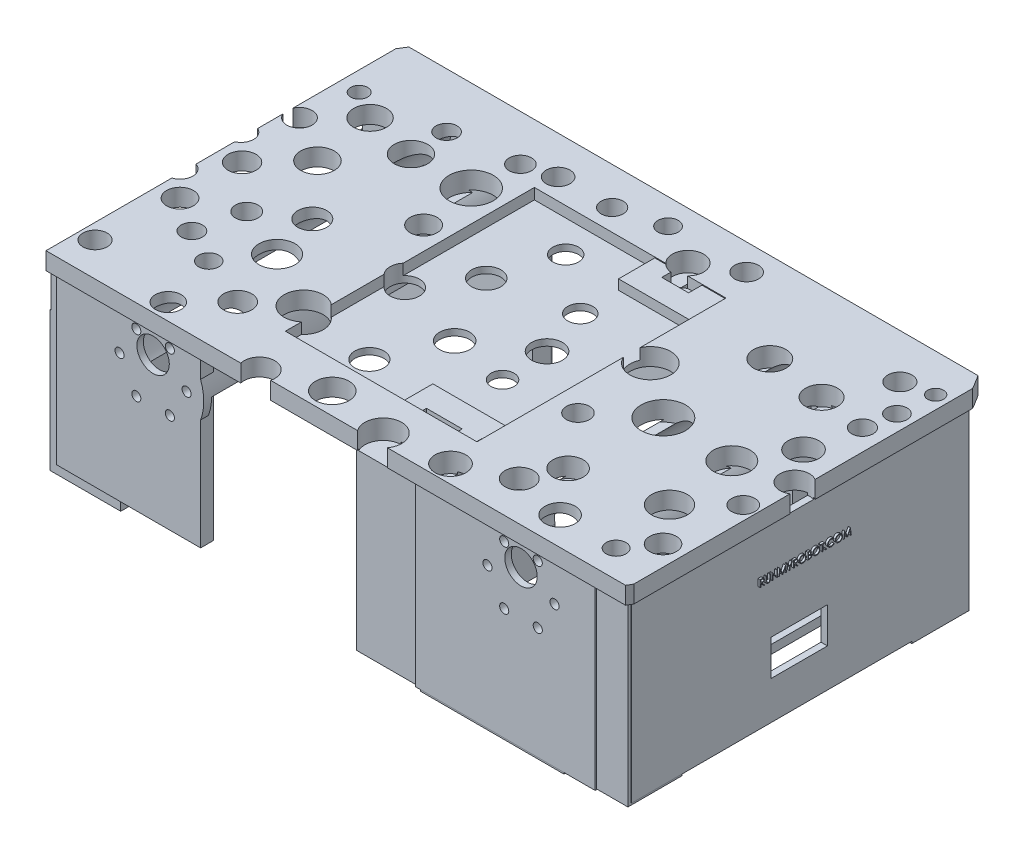
SolidWorks part; units mm, degrees
ref_plane "Front Plane" through (0, 0, 0) normal (0, 0, 1) x (1, 0, 0)
ref_plane "Top Plane" through (0, 0, 0) normal (0, 1, 0) x (1, 0, 0)
ref_plane "Right Plane" through (0, 0, 0) normal (1, 0, 0) x (0, 0, -1)
sketch "MotorHoldersSketch" plane through (0, 0, 0) normal (0, 0, 1) x (1, 0, 0)
  line L0 (0, 0) -> (170, 0) construction
  line L1 (0, 0) -> (0, 23.41) construction
  line L2 (170, 0) -> (170, 23.41) construction
  circle A0 centre (0, 0) radius 23.41
  circle A1 centre (170, 0) radius 23.41
ref_axis "MotorCenterAxis1" through (0, 0, 0) along (0, 0, 1)
ref_axis "MotorCenterAxis2" through (170, 0, 0) along (0, 0, 1)
extrude "MotorHolders" add sketch "MotorHoldersSketch" along normal blind 80 and the other way blind 80
sketch "Sketch3" plane through (0, 0, 0) normal (0, 0, 1) x (1, 0, 0)
  line L1 (1.9406, 21.133) -> (168.3435, 21.133)
  line L2 (1.9406, 21.133) -> (1.9406, 18.3155)
  line L3 (1.9406, 18.3155) -> (168.3435, 18.3155)
  line L4 (168.3435, 21.133) -> (168.3435, 18.3155)
sketch "Sketch4" plane through (0, 0, 0) normal (0, 1, 0) x (1, 0, 0)
  line L1 (221.2811, -76.3794) -> (-41.4939, -76.3794)
  line L2 (221.2811, -76.3794) -> (221.2811, 76.7331)
  line L3 (221.2811, 76.7331) -> (-41.4939, 76.7331)
  line L4 (-41.4939, -76.3794) -> (-41.4939, 76.7331)
extrude "Cut-Extrude1" cut sketch "Sketch4" against normal blind 26
ref_axis "Axis3" through (170, 0, 0) along (0, -1, 0)
sketch3d "ReferencePlanePosition"
  line L0 (170, 0, 0) -> (170, -34.8293, 0)
  line L1 (170, 0, 0) -> (170, -38.994, 0) construction
ref_plane "ReferencePlane" through (170, -34.8293, 0) normal (0, -1, 0) x (-1, 0, 0)
sketch "Sketch6" plane through (170, -34.8293, 0) normal (0, -1, 0) x (-1, 0, 0)
  line L1 (219.5858, 78.949) -> (145.1716, 78.949)
  line L2 (219.5858, 78.949) -> (219.5858, 65.5282)
  line L3 (219.5858, 65.5282) -> (145.1716, 65.5282)
  line L4 (145.1716, 78.949) -> (145.1716, 65.5282)
  line L5 (219.3147, -52.1095) -> (186.667, -52.1095)
  line L6 (219.3147, -52.1095) -> (219.3147, -78.2822)
  line L7 (219.3147, -78.2822) -> (186.667, -78.2822)
  line L8 (186.667, -52.1095) -> (186.667, -78.2822)
  line L9 (75.6651, 77.8627) -> (19.9904, 77.8627)
  line L10 (75.6651, 77.8627) -> (75.6651, 40.7512)
  line L11 (75.6651, 40.7512) -> (19.9904, 40.7512)
  line L12 (19.9904, 77.8627) -> (19.9904, 40.7512)
  line L13 (76.5596, -44.1716) -> (20.0852, -44.1716)
  line L14 (76.5596, -44.1716) -> (76.5596, -79.4437)
  line L15 (76.5596, -79.4437) -> (20.0852, -79.4437)
  line L16 (20.0852, -44.1716) -> (20.0852, -79.4437)
  line L17 (213.765, 73.0364) -> (192.9548, 73.0364)
  line L18 (213.765, 73.0364) -> (213.765, 71.0153)
  line L19 (213.765, 71.0153) -> (192.9548, 71.0153)
  line L20 (192.9548, 73.0364) -> (192.9548, 71.0153)
  line L21 (41.3552, 69.1777) -> (28.5109, 69.1777)
  line L22 (41.3552, 69.1777) -> (41.3552, 50.8413)
  line L23 (41.3552, 50.8413) -> (28.5109, 50.8413)
  line L24 (28.5109, 69.1777) -> (28.5109, 50.8413)
  line L25 (43.3068, -72.8101) -> (32.1723, -72.8101)
  line L26 (43.3068, -72.8101) -> (43.3068, -54.7747)
  line L27 (43.3068, -54.7747) -> (32.1723, -54.7747)
  line L28 (32.1723, -72.8101) -> (32.1723, -54.7747)
  line L29 (211.9411, -70.4881) -> (201.0982, -70.4881)
  line L30 (211.9411, -70.4881) -> (211.9411, -60.1404)
  line L31 (211.9411, -60.1404) -> (201.0982, -60.1404)
  line L32 (201.0982, -70.4881) -> (201.0982, -60.1404)
  line L37 (66.2772, 51.3198) -> (53.8697, 51.3198)
  line L38 (66.2772, 51.3198) -> (66.2772, 67.7632)
  line L39 (66.2772, 67.7632) -> (53.8697, 67.7632)
  line L40 (53.8697, 51.3198) -> (53.8697, 67.7632)
  line L45 (68.2481, -69.8638) -> (51.7107, -69.8638)
  line L46 (68.2481, -69.8638) -> (68.2481, -55.4273)
  line L47 (68.2481, -55.4273) -> (51.7107, -55.4273)
  line L48 (51.7107, -69.8638) -> (51.7107, -55.4273)
  line L49 (-20.7001, -79.4437) -> (-48.8506, -79.4437)
  line L50 (-20.7001, -79.4437) -> (-20.7001, -54.5097)
  line L51 (-20.7001, -54.5097) -> (-48.8506, -54.5097)
  line L52 (-48.8506, -79.4437) -> (-48.8506, -54.5097)
  line L53 (-18.3873, 77.8627) -> (-49.0581, 77.8627)
  line L54 (-18.3873, 77.8627) -> (-18.3873, 51.5325)
  line L55 (-18.3873, 51.5325) -> (-49.0581, 51.5325)
  line L56 (-49.0581, 77.8627) -> (-49.0581, 51.5325)
  line L57 (-41.8141, -72.8101) -> (-31.6362, -72.8101)
  line L58 (-41.8141, -72.8101) -> (-41.8141, -62.9794)
  line L59 (-41.8141, -62.9794) -> (-31.6362, -62.9794)
  line L60 (-31.6362, -72.8101) -> (-31.6362, -62.9794)
  line L61 (-31.6362, 69.1777) -> (-41.5347, 69.1777)
  line L62 (-31.6362, 69.1777) -> (-31.6362, 58.5421)
  line L63 (-31.6362, 58.5421) -> (-41.5347, 58.5421)
  line L64 (-41.5347, 69.1777) -> (-41.5347, 58.5421)
extrude "PowerBankHolders" add sketch "Sketch6" along normal blind 30 and the other way blind 59 separate body
sketch3d "3DSketch3"
  line L0 (170, 0, 0) -> (170, -64.5, 0) construction
ref_plane "Plane2" through (170, -64.5, 0) normal (0, -1, 0) x (-1, 0, 0)
sketch "Sketch7" plane through (170, -64.5, 0) normal (0, -1, 0) x (-1, 0, 0)
  line L1 (-9.5047, -80.801) -> (181.32, -80.801)
  line L2 (-9.5047, -80.801) -> (-9.5047, 73.8662)
  line L3 (-9.5047, 73.8662) -> (181.32, 73.8662)
  line L4 (181.32, -80.801) -> (181.32, 73.8662)
  line L5 (151.8712, -54.3972) -> (26.5361, -54.3972)
  line L6 (151.8712, -54.3972) -> (151.8712, 46.2413)
  line L7 (151.8712, 46.2413) -> (26.5361, 46.2413)
  line L8 (26.5361, -54.3972) -> (26.5361, 46.2413)
ref_point "Point1"
ref_point "Point2"
sketch3d "3DSketch11"
  line L0 (0, 0, -80) -> (170, 0, 80) construction
  point P4 (85, 0, 0)
sketch "MotorHolderExtrudeSketch" plane through (0, 0, 0) normal (0, 0, 1) x (1, 0, 0)
  circle A0 centre (170, 0) radius 20.415
  circle A1 centre (0, 0) radius 20.415
  circle A3 centre (0, 0) radius 23.41 construction
  circle A4 centre (170, 0) radius 23.41 construction
ref_point "TopOfMotors"
ref_plane "TangentToTopOfMotors" through (0, -20.415, 0) normal (0, 1, 0) x (1, 0, 0)
ref_axis "Axis4" through (85, 0, 0) along (0, -1, 0)
ref_plane "BottomOfPowerBankRegion" through (0, -20.425, 0) normal (0, 1, 0) x (1, 0, 0)
sketch "Sketch11" plane through (0, -20.425, 0) normal (0, 1, 0) x (1, 0, 0)
  line L0 (-18.9327, 3.7419) -> (188.9327, -3.7419) construction
  line L5 (-18.9327, -64.7581) -> (-18.9327, 72.2419)
  line L6 (188.9327, 63.7581) -> (188.9327, -71.2419)
  line L7 (188.9327, -71.2419) -> (-18.9327, -64.7581)
  line L8 (188.9327, 63.7581) -> (-18.9327, 72.2419)
  circle A0 centre (85, 0) radius 104 construction
ref_point "CenterAtBottomOfPowerBank"
ref_plane "TopOfPowerBankPlane" through (0, -54.425, 0) normal (0, 1, 0) x (1, 0, 0)
sketch "Sketch13" plane through (0, -54.425, 0) normal (0, 1, 0) x (1, 0, 0)
  line L1 (-19.4498, 72.5454) -> (166.1636, 72.5454)
  line L2 (-19.4498, 72.5454) -> (-19.4498, -78.2051)
  line L3 (-19.4498, -78.2051) -> (166.1636, -78.2051)
  line L4 (166.1636, 72.5454) -> (166.1636, -78.2051)
  line L5 (19.3173, -49.583) -> (137.9607, -49.583)
  line L6 (19.3173, -49.583) -> (19.3173, -21.0549)
  line L7 (19.3173, -21.0549) -> (137.9607, -21.0549)
  line L8 (137.9607, -49.583) -> (137.9607, -21.0549)
  line L9 (19.3173, 56.6778) -> (137.9607, 56.6778)
  line L10 (19.3173, 56.6778) -> (19.3173, 36.3234)
  line L11 (19.3173, 36.3234) -> (137.9607, 36.3234)
  line L12 (137.9607, 56.6778) -> (137.9607, 36.3234)
  line L13 (19.3173, 18.3186) -> (137.9607, 18.3186)
  line L14 (19.3173, 18.3186) -> (19.3173, -7.3615)
  line L15 (19.3173, -7.3615) -> (137.9607, -7.3615)
  line L16 (137.9607, 18.3186) -> (137.9607, -7.3615)
sketch "Sketch15" plane through (150.0096, 0, 0) normal (1, 0, 0) x (0, 0, -1)
  line L1 (72.5313, -25.7765) -> (45.7099, -25.7765)
  line L2 (72.5313, -25.7765) -> (72.5313, -24.2242)
  line L3 (72.5313, -24.2242) -> (45.7099, -24.2242)
  line L4 (45.7099, -25.7765) -> (45.7099, -24.2242)
extrude "PowerBankCut" cut sketch "Sketch11" against normal blind 64
ref_plane "Plane6" through (0, 0, 0) normal (0, 0, 1) x (1, 0, 0)
sketch "MotorGeometry1" plane through (0, 0, 0) normal (0, 0, 1) x (1, 0, 0)
  line L0 (170, 0) -> (170, -13.42)
  line L1 (170, 0) -> (170, -34.8293) construction
  line L2 (170, -13.42) -> (162.25, -13.42) construction
  line L3 (170, -13.42) -> (177.75, -13.42) construction
  line L4 (170, -13.42) -> (170, 7) construction
  line L5 (170, 0) -> (185.5, 0) construction
  line L6 (170, 0) -> (154.5, 0) construction
  line L7 (170, 0) -> (170, 13.42) construction
  line L8 (170, 0) -> (170, 23.41) construction
  line L9 (170, 13.42) -> (177.75, 13.42) construction
  line L10 (170, 13.42) -> (162.25, 13.42)
ref_axis "BoltAxisA" through (185.5, 0, 0) along (0, 0, 1)
ref_axis "BoltAxisB" through (177.75, -13.42, 0) along (0, 0, 1)
ref_axis "BoltAxisC" through (162.25, -13.42, 0) along (0, 0, 1)
ref_axis "BoltAxisD" through (154.5, 0, 0) along (0, 0, 1)
ref_axis "BoltAxisE" through (162.25, 13.42, 0) along (0, 0, 1)
ref_axis "BoltAxisF" through (177.75, 13.42, 0) along (0, 0, 1)
ref_point "Point6"
ref_point "Point7"
ref_point "Point8"
ref_point "Point9"
ref_point "Point10"
ref_point "Point11"
ref_point "Point12"
ref_point "Point13"
ref_point "Point14"
ref_point "Point15"
ref_point "Point16"
ref_point "Point17"
ref_plane "Plane7" through (0, 0, 0) normal (0, 0, 1) x (1, 0, 0)
sketch "MotorGeometry2" plane through (0, 0, 0) normal (0, 0, 1) x (1, 0, 0)
  line L0 (0, 0) -> (0, -13.42) construction
  line L1 (0, -13.42) -> (7.75, -13.42) construction
  line L2 (0, -13.42) -> (-7.75, -13.42) construction
  line L3 (0, 0) -> (0, 13.42)
  line L4 (0, -13.42) -> (0, 7) construction
  line L5 (0, 13.42) -> (7.75, 13.42) construction
  line L6 (0, 13.42) -> (-7.75, 13.42) construction
  line L7 (0, 0) -> (15.5, 0) construction
  line L8 (0, 0) -> (-15.5, 0) construction
  line L9 (0, 0) -> (0, 23.41) construction
ref_axis "Axis11" through (15.5, 0, 0) along (0, 0, 1)
ref_axis "Axis12" through (7.75, 13.42, 0) along (0, 0, 1)
ref_axis "Axis13" through (-7.75, 13.42, 0) along (0, 0, 1)
ref_axis "Axis14" through (-15.5, 0, 0) along (0, 0, 1)
ref_axis "Axis15" through (-7.75, -13.42, 0) along (0, 0, 1)
ref_axis "Axis16" through (7.75, -13.42, 0) along (0, 0, 1)
ref_point "Point18"
ref_point "Point19"
ref_point "Point20"
ref_point "Point21"
ref_point "Point22"
ref_point "Point23"
ref_point "Point24"
ref_point "Point25"
ref_point "Point26"
ref_point "Point27"
ref_point "Point28"
ref_point "Point29"
ref_plane "BottomPlane" through (0, 19.575, 0) normal (0, 1, 0) x (1, 0, 0)
ref_axis "OutputShaftReference1" through (0, 7, 0) along (0, 0, 1)
ref_point "Point35"
ref_axis "OutputShaftReference2" through (170, 7, 0) along (0, 0, 1)
sketch "Sketch21" plane through (0, 19.575, 0) normal (0, 1, 0) x (1, 0, 0)
  line L0 (219.6842, -79.5488) -> (-50.341, -79.5488) construction
  line L1 (-50.341, -79.5488) -> (-50.341, 79.7899) construction
  line L2 (-50.341, 79.7899) -> (219.6842, 79.7899) construction
  line L3 (219.6842, 79.7899) -> (219.6842, -79.5488) construction
  line L4 (127.2472, -57.5918) -> (127.2472, 57.4773)
  line L5 (127.2472, 57.4773) -> (38.7099, 57.4773)
  line L6 (38.7099, 57.4773) -> (38.7099, -57.5918)
  line L7 (38.7099, -57.5918) -> (127.2472, -57.5918)
  circle A0 centre (85, 0) radius 156.3953
extrude "BottomPlate" add sketch "Sketch21" along normal blind 5 and the other way blind 3
ref_plane "HoleReferencePlane1" through (0, 0, 80) normal (0, 0, 1) x (1, 0, 0)
ref_point "OutputShaftPosition3"
ref_point "OutputShaftPosition1"
sketch "Sketch23" plane through (0, 0, 80) normal (0, 0, 1) x (1, 0, 0)
  line L1 (21.9586, -59.3229) -> (-44.5901, -59.3229)
  line L2 (21.9586, -59.3229) -> (21.9586, 21.8402)
  line L3 (21.9586, 21.8402) -> (-44.5901, 21.8402)
  line L4 (-44.5901, -59.3229) -> (-44.5901, 21.8402)
  line L5 (121.3218, 21.8402) -> (204.258, 21.8402)
  line L6 (121.3218, 21.8402) -> (121.3218, -65.2231)
  line L7 (121.3218, -65.2231) -> (204.258, -65.2231)
  line L8 (204.258, 21.8402) -> (204.258, -65.2231)
extrude "MotorMountingSupport1" add sketch "Sketch23" against normal blind 6
ref_plane "HoleReferencePlane2" through (0, 0, -80) normal (0, 0, -1) x (-1, 0, 0)
ref_point "OutputShaftPosition4"
ref_point "OutputShaftPosition2"
sketch "Sketch24" plane through (0, 0, -80) normal (0, 0, -1) x (-1, 0, 0)
  line L1 (-202.1905, -67.1257) -> (-139.5471, -67.1257)
  line L2 (-202.1905, -67.1257) -> (-202.1905, 19.2374)
  line L3 (-202.1905, 19.2374) -> (-139.5471, 19.2374)
  line L4 (-139.5471, -67.1257) -> (-139.5471, 19.2374)
  line L5 (-24.3642, -64.1521) -> (29.5505, -64.1521)
  line L6 (-24.3642, -64.1521) -> (-24.3642, 22.5226)
  line L7 (-24.3642, 22.5226) -> (29.5505, 22.5226)
  line L8 (29.5505, -64.1521) -> (29.5505, 22.5226)
extrude "MotorMountingSuppor2" add sketch "Sketch24" against normal blind 6
sketch "Sketch17" plane through (0, 0, 80) normal (0, 0, 1) x (1, 0, 0)
  circle A0 centre (185.5, 0) radius 2.1
  circle A1 centre (177.75, -13.42) radius 2.1
  circle A2 centre (162.25, -13.42) radius 2.1
  circle A3 centre (154.5, 0) radius 2.1
  circle A4 centre (162.25, 13.42) radius 2.1
  circle A5 centre (177.75, 13.42) radius 2.1
  circle A6 centre (170, 7) radius 7.5
extrude "MotorHoles1" cut sketch "Sketch17" against normal blind 31.5
sketch "Sketch19" plane through (0, 0, -80) normal (0, 0, -1) x (-1, 0, 0)
  circle A0 centre (-185.5, 0) radius 2.1
  circle A1 centre (-177.75, -13.42) radius 2.1
  circle A2 centre (-162.25, -13.42) radius 2.1
  circle A3 centre (-154.5, 0) radius 2.1
  circle A4 centre (-162.25, 13.42) radius 2.1
  circle A5 centre (-177.75, 13.42) radius 2.1
  circle A6 centre (-170, 7) radius 7.5
sketch "BoltHolesSketch3" plane through (0, 0, 80) normal (0, 0, 1) x (1, 0, 0)
  circle A0 centre (7.75, -13.42) radius 2.1
  circle A1 centre (15.5, 0) radius 2.1
  circle A2 centre (7.75, 13.42) radius 2.1
  circle A3 centre (-7.75, 13.42) radius 2.1
  circle A4 centre (-15.5, 0) radius 2.1
  circle A5 centre (-7.75, -13.42) radius 2.1
  circle A6 centre (0, 7) radius 7.5
extrude "Cut-Extrude4" cut sketch "Sketch19" against normal blind 30
extrude "MotorHoles3" cut sketch "BoltHolesSketch3" against normal blind 31.5
sketch "BoltHolesSketch4" plane through (0, 0, -80) normal (0, 0, -1) x (-1, 0, 0)
  circle A0 centre (-15.5, 0) radius 2.1
  circle A1 centre (-7.75, 13.42) radius 2.1
  circle A2 centre (7.75, 13.42) radius 2.1
  circle A3 centre (15.5, 0) radius 2.1
  circle A4 centre (7.75, -13.42) radius 2.1
  circle A5 centre (-7.75, -13.42) radius 2.1
  circle A6 centre (0, 7) radius 7.5
extrude "MotorHoles4" cut sketch "BoltHolesSketch4" against normal blind 15
ref_plane "Front" through (219.0581, 0, 0) normal (1, 0, 0) x (0, 0, -1)
sketch "Sketch29" plane through (219.0581, 0, 0) normal (1, 0, 0) x (0, 0, -1)
  line L1 (76.6955, -63.9254) -> (-77.9397, -63.9254)
  line L2 (76.6955, -63.9254) -> (76.6955, 20.2062)
  line L3 (76.6955, 20.2062) -> (-77.9397, 20.2062)
  line L4 (-77.9397, -63.9254) -> (-77.9397, 20.2062)
  line L5 (-13.4507, -46.2559) -> (12.5493, -46.2559)
  line L6 (-13.4507, -46.2559) -> (-13.4507, -29.7559)
  line L7 (-13.4507, -29.7559) -> (12.5493, -29.7559)
  line L8 (12.5493, -46.2559) -> (12.5493, -29.7559)
extrude "Boss-Extrude8" add sketch "Sketch29" against normal blind 3
ref_plane "RaspberryPiBasePlane" through (0, 16.575, 0) normal (0, -1, 0) x (-1, 0, 0)
sketch "Sketch27" plane through (0, 16.575, 0) normal (0, -1, 0) x (-1, 0, 0)
  line L1 (31.6337, 64.5517) -> (-194.8264, 64.5517)
  line L2 (31.6337, 64.5517) -> (31.6337, -65.4335)
  line L3 (31.6337, -65.4335) -> (-194.8264, -65.4335)
  line L4 (-194.8264, 64.5517) -> (-194.8264, -65.4335)
extrude "Boss-Extrude6" add sketch "Sketch27" against normal blind 3
ref_plane "Plane12" through (0, -64.8293, 0) normal (0, -1, 0) x (-1, 0, 0)
sketch "Sketch28" plane through (0, -64.8293, 0) normal (0, -1, 0) x (-1, 0, 0)
  line L1 (-189.3897, -79.549) -> (-123.0026, -79.549)
  line L2 (-189.3897, -79.549) -> (-189.3897, 78.1499)
  line L3 (-189.3897, 78.1499) -> (-123.0026, 78.1499)
  line L4 (-123.0026, -79.549) -> (-123.0026, 78.1499)
extrude "Boss-Extrude7" add sketch "Sketch28" along normal blind 1.5 and the other way blind 2.5
extrude "MotorHolderCut" cut sketch "MotorHolderExtrudeSketch" against normal blind 77 and the other way blind 77
sketch "Sketch31" plane through (219.0581, 0, 0) normal (1, 0, 0) x (0, 0, -1)
  text T0 "RUNMYROBOT.COM"
extrude "Boss-Extrude9" add sketch "Sketch31" along normal blind 1
sketch "Sketch32" plane through (0, 19.575, 0) normal (0, 1, 0) x (1, 0, 0)
  line L1 (-48.8137, 84.6887) -> (220.392, 84.6887)
  line L2 (-48.8137, 84.6887) -> (-48.8137, -80.6635)
  line L3 (-48.8137, -80.6635) -> (220.392, -80.6635)
  line L4 (220.392, 84.6887) -> (220.392, -80.6635)
  line L5 (283.5566, -218.7268) -> (-136.4889, -218.7268)
  line L8 (-136.4889, -218.7268) -> (-136.4889, 206.3198)
  line L10 (283.5566, 206.3198) -> (283.5566, -218.7268)
  line L13 (283.5566, 206.3198) -> (-136.4889, 206.3198)
extrude "Cut-Extrude5" cut sketch "Sketch32" along normal blind 20 and the other way blind 20
sketch "Sketch33" plane through (0, 19.575, 0) normal (0, 1, 0) x (1, 0, 0)
  circle A0 centre (-22.9931, -39.0817) radius 4.8787
  circle A1 centre (-38.869, -28.6758) radius 6.1814
  circle A2 centre (-38.869, 0) radius 6.4339
  circle A3 centre (-18.1144, -18.6246) radius 5.2179
  circle A4 centre (-7.0605, -47.2054) radius 4.66
  circle A5 centre (0, -72.9746) radius 5.9667
  circle A6 centre (15.9496, -56.859) radius 6.4937
  circle A7 centre (5.9667, -28.6758) radius 8.3698
  circle A8 centre (0, -6.4339) radius 6.705
  circle A9 centre (48.0835, -78.9413) radius 7.1141
  circle A10 centre (32.8401, -43.2654) radius 9.0432
  circle A11 centre (28.1751, 16.8372) radius 6.2158
  circle A12 centre (43.8559, -7.5426) radius 6.7892
  circle A13 centre (58.936, 15.0095) radius 6.7892
  circle A14 centre (76.6957, -17.3438) radius 6.9689
  circle A15 centre (64.4096, -44.467) radius 6.7406
  circle A16 centre (103.323, -21.8535) radius 5.3241
  circle A17 centre (94.8111, 22.58) radius 5.8135
  circle A18 centre (67.8036, 42.8533) radius 5.9527
  circle A19 centre (-3.1562, 42.3102) radius 7.7513
  circle A20 centre (-22.1014, 18.0609) radius 7.7765
  circle A21 centre (-27.0861, 47.354) radius 7.5936
  circle A22 centre (24.3642, 42.6359) radius 10.2123
  circle A23 centre (139.0292, -22.7018) radius 5.3241
  circle A24 centre (102.2156, -0.1778) radius 7.1367
  circle A25 centre (135.8338, 13.9334) radius 9.4137
  circle A26 centre (160.6809, -4.9043) radius 10.2864
  circle A27 centre (161.6975, 43.2796) radius 7.4945
  circle A28 centre (189.0429, 39.8439) radius 7.3614
  circle A29 centre (196.8791, -38.2646) radius 8.24
  circle A30 centre (193.6897, -6.2867) radius 8.5005
  circle A31 centre (205.8039, 14.7463) radius 7.133
  circle A32 centre (214.0351, -21.3574) radius 5.3439
  circle A33 centre (210.6314, 37.1315) radius 4.944
  circle A34 centre (200.973, 64.1015) radius 5.5788
  circle A35 centre (201.9543, -68.0057) radius 4.5697
  circle A36 centre (-41.7795, -65.0306) radius 5.5788
  circle A37 centre (-43.4335, 31.0728) radius 5.8514
  circle A38 centre (-39.8672, 55.0716) radius 3.9193
  circle A39 centre (-3.808, 59.4176) radius 4.8545
  circle A40 centre (26.2257, 63.502) radius 5.1675
  circle A41 centre (39.9813, 67.1578) radius 5.501
  circle A42 centre (64.7138, 67.3973) radius 5.113
  circle A43 centre (85.1224, 72.8365) radius 4.7075
  circle A44 centre (104.4721, 62.693) radius 7.2191
  circle A45 centre (121.6372, 72.6142) radius 5.5163
  circle A46 centre (73.4374, -70.6302) radius 7.7765
  circle A47 centre (102.044, -75.6796) radius 8.4931
  circle A48 centre (129.9204, -72.4882) radius 7.1458
  circle A49 centre (151.7623, -62.5725) radius 6.5365
  circle A50 centre (158.9372, -47.1761) radius 6.978
  circle A51 centre (175.6921, -67.6164) radius 6.9689
  circle A52 centre (211.1116, -55.4776) radius 6.1459
  circle A53 centre (213.0421, 50.6527) radius 4.7003
  circle A54 centre (214.3696, 67.2204) radius 3.6558
  circle A55 centre (216.7958, -0.3133) radius 6.7911
  circle A56 centre (-50.566, -16.9247) radius 5.8514
  circle A57 centre (-51.233, 11.8259) radius 5.8477
extrude "Cut-Extrude6" cut sketch "Sketch33" against normal blind 4 and the other way blind 6
